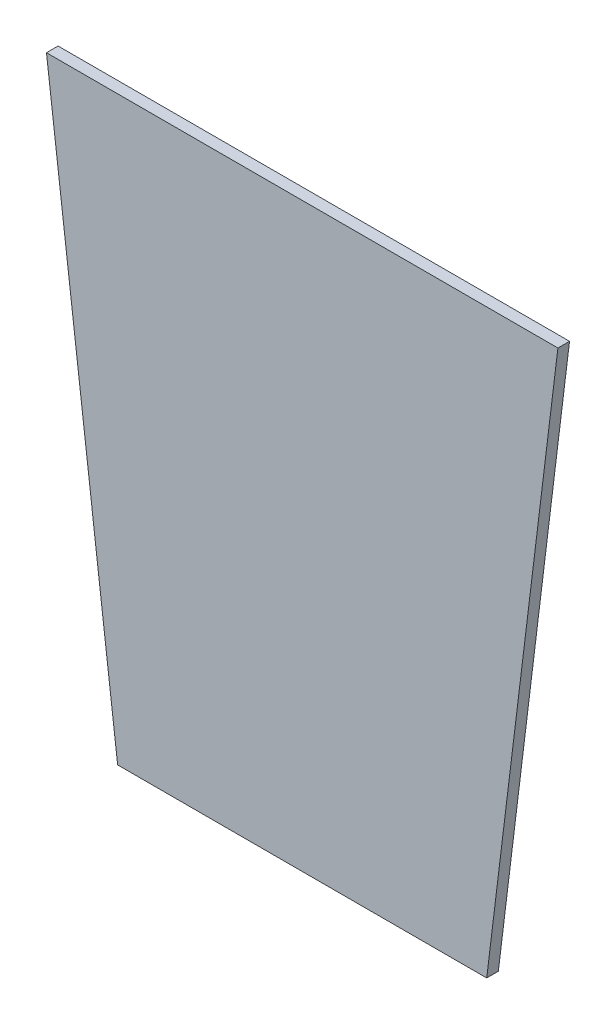
SolidWorks part; units mm, degrees
note: The reader was unsure of these and kept them because the rebuilt part matched: thickness of "Base-Flange1", "Sheet-Metal(1)".
ref_plane "Front Plane" through (0, 0, 0) normal (0, 0, 1) x (1, 0, 0)
ref_plane "Top Plane" through (0, 0, 0) normal (0, 1, 0) x (1, 0, 0)
ref_plane "Right Plane" through (0, 0, 0) normal (1, 0, 0) x (0, 0, -1)
sketch "Sketch1" plane through (0, 0, 0) normal (0, 0, 1) x (1, 0, 0)
  line L0 (-88, 200) -> (88, 200)
  line L1 (88, 200) -> (63.5, 0)
  line L2 (63.5, 0) -> (-63.5, 0)
  line L3 (-63.5, 0) -> (-88, 200)
  line L4 (0, 200) -> (0, 0) construction
  dimension "D1" = 127
  dimension "D2" = 176
  dimension "D3" = 200
base flange "Base-Flange1" sketch "Sketch1" thickness 4 reverse thickness direction no parameters "D1"=0.5
sketch "Bend-Lines1" plane through (0, 0, 0) normal (0, 1, 0) x (1, 0, 0)
sketch "Bounding-Box1" plane through (0, 0, 0) normal (0, 1, 0) x (1, 0, 0)
sheet metal parameters "Sheet-Metal(1)" thickness 4 parameters "D1"=0.5
flat pattern "Flat-Pattern(1)" [suppressed]
sketch "Bend-Lines2" plane through (0, 0, 0) normal (0, 1, 0) x (1, 0, 0)
sketch "Bounding-Box2" [suppressed] plane through (0, 0, 0) normal (0, 1, 0) x (1, 0, 0)
